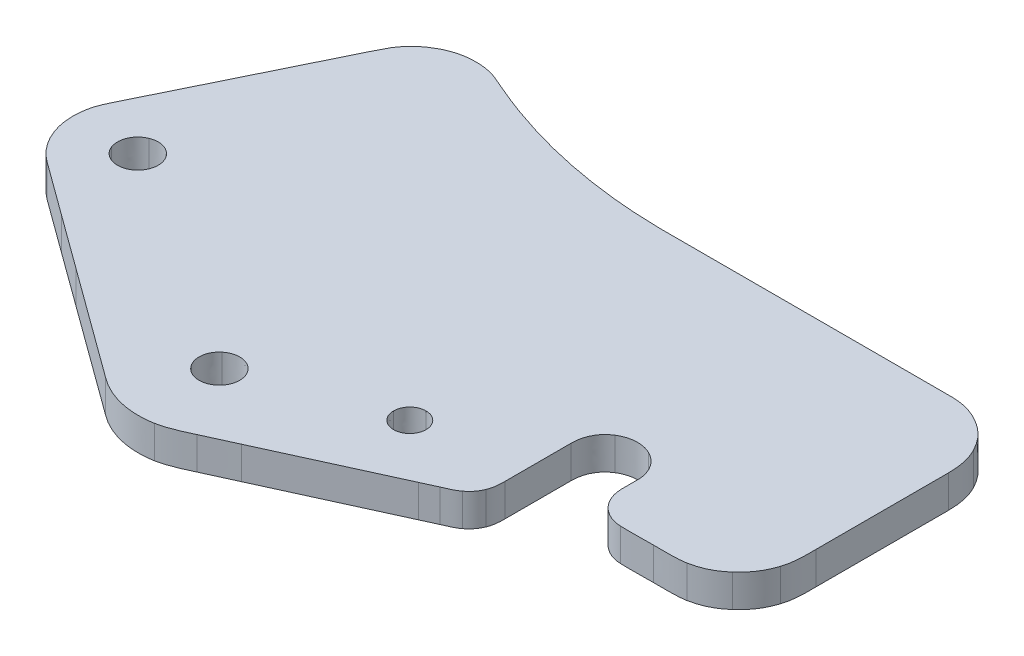
SolidWorks part; units mm, degrees
ref_plane "Front Plane" through (0, 0, 0) normal (0, 0, 1) x (1, 0, 0)
ref_plane "Top Plane" through (0, 0, 0) normal (0, 1, 0) x (1, 0, 0)
ref_plane "Right Plane" through (0, 0, 0) normal (1, 0, 0) x (0, 0, -1)
sketch "Imported Profile" plane through (0, 0, 0) normal (0, 1, 0) x (1, 0, 0)
  spline S0 degree 3 poles (47.6488, 3.4753) (40.593, 8.6202) (33.5375, 13.7602) (26.4819, 18.9072) knots 0 0 0 0 1 1 1 1
  spline S1 degree 3 poles (26.4819, 18.9072) (22.961, 21.4772) (19.4332, 24.0473) (15.9054, 26.6173) knots 0 0 0 0 1 1 1 1
  spline S2 degree 3 poles (15.9054, 26.6173) (12.3776, 29.1943) (8.8292, 31.7229) (5.329, 34.3343) knots 0 0 0 0 1 1 1 1
  spline S3 degree 3 poles (5.329, 34.3343) (1.7254, 37.0215) (-0.1832, 41.3968) (0.2923, 45.8616) knots 0 0 0 0 1 1 1 1
  spline S4 degree 3 poles (0.2923, 45.8616) (0.5679, 48.4454) (1.3534, 49.7752) (2.4489, 52.0214) knots 0 0 0 0 1 1 1 1
  spline S5 degree 3 poles (2.4489, 52.0214) (3.4066, 53.9851) (4.3713, 55.942) (5.329, 57.8988) knots 0 0 0 0 1 1 1 1
  spline S6 degree 3 poles (5.329, 57.8988) (9.1599, 65.7398) (12.9978, 73.5809) (16.8287, 81.4288) knots 0 0 0 0 1 1 1 1
  spline S7 degree 3 poles (16.8287, 81.4288) (17.2628, 82.3038) (19.1783, 86.3001) (19.7019, 87.1339) knots 0 0 0 0 1 1 1 1
  spline S8 degree 3 poles (19.7019, 87.1339) (20.9491, 89.1182) (22.4649, 90.5238) (24.532, 91.6194) knots 0 0 0 0 1 1 1 1
  spline S9 degree 3 poles (24.532, 91.6194) (26.6886, 92.7563) (28.7694, 93.2041) (31.2086, 93.0595) knots 0 0 0 0 1 1 1 1
  spline S10 degree 3 poles (31.2086, 93.0595) (33.8062, 92.9079) (34.9913, 92.2395) (37.2926, 91.2473) knots 0 0 0 0 1 1 1 1
  spline S11 degree 3 poles (37.2926, 91.2473) (45.3403, 87.754) (53.5052, 85.3975) (62.18, 84.0608) knots 0 0 0 0 1 1 1 1
  spline S12 degree 3 poles (62.18, 84.0608) (71.9503, 82.5519) (78.5373, 82.8688) (88.3283, 82.8688) knots 0 0 0 0 1 1 1 1
  spline S13 degree 3 poles (88.3283, 82.8688) (97.065, 82.8688) (105.8018, 82.8688) (114.5317, 82.8688) knots 0 0 0 0 1 1 1 1
  spline S14 degree 3 poles (114.5317, 82.8688) (118.8518, 82.8688) (123.1719, 82.8688) (127.499, 82.8688) knots 0 0 0 0 1 1 1 1
  spline S15 degree 3 poles (127.499, 82.8688) (129.6487, 82.8688) (131.7985, 82.9378) (133.9413, 82.8638) knots 0 0 0 0 1 1 1 1
  spline S16 degree 3 poles (133.9413, 82.8638) (136.2426, 82.7813) (138.1926, 82.1886) (140.1494, 80.9759) knots 0 0 0 0 1 1 1 1
  spline S17 degree 3 poles (140.1494, 80.9759) (142.244, 79.6874) (143.6978, 78.1096) (144.8071, 75.9116) knots 0 0 0 0 1 1 1 1
  spline S18 degree 3 poles (144.8071, 75.9116) (145.8338, 73.8928) (146.1783, 71.8946) (146.1783, 69.6692) knots 0 0 0 0 1 1 1 1
  spline S19 degree 3 poles (146.1783, 69.6692) (146.1783, 65.3489) (146.1783, 61.022) (146.1783, 56.7017) knots 0 0 0 0 1 1 1 1
  spline S20 degree 3 poles (146.1783, 56.7017) (146.1783, 52.3954) (146.1783, 48.089) (146.1783, 43.7827) knots 0 0 0 0 1 1 1 1
  spline S21 degree 3 poles (146.1783, 43.7827) (146.1783, 41.6536) (146.2543, 39.5865) (145.5788, 37.485) knots 0 0 0 0 1 1 1 1
  spline S22 degree 3 poles (145.5788, 37.485) (144.8416, 35.1768) (143.6909, 33.4061) (141.865, 31.8006) knots 0 0 0 0 1 1 1 1
  spline S23 degree 3 poles (141.865, 31.8006) (140.0805, 30.2296) (138.2063, 29.3133) (135.8637, 28.8654) knots 0 0 0 0 1 1 1 1
  spline S24 degree 3 poles (135.8637, 28.8654) (134.2514, 28.5624) (131.137, 28.6449) (129.5247, 28.6449) knots 0 0 0 0 1 1 1 1
  spline S25 degree 3 poles (129.5247, 28.6449) (127.3818, 28.6449) (125.2321, 28.5624) (123.0893, 28.6449) knots 0 0 0 0 1 1 1 1
  spline S26 degree 3 poles (123.0893, 28.6449) (120.7879, 28.7344) (118.714, 30.0574) (117.6736, 32.1107) knots 0 0 0 0 1 1 1 1
  spline S27 degree 3 poles (117.6736, 32.1107) (116.5849, 34.2328) (117.0741, 36.3137) (116.9708, 38.4427) knots 0 0 0 0 1 1 1 1
  spline S28 degree 3 poles (116.9708, 38.4427) (116.8538, 40.751) (115.5032, 42.8042) (113.4292, 43.824) knots 0 0 0 0 1 1 1 1
  spline S29 degree 3 poles (113.4292, 43.824) (111.4448, 44.8024) (109.1022, 44.6715) (107.2349, 43.4935) knots 0 0 0 0 1 1 1 1
  spline S30 degree 3 poles (107.2349, 43.4935) (105.1885, 42.1981) (104.279, 40.1655) (104.279, 37.8228) knots 0 0 0 0 1 1 1 1
  spline S31 degree 3 poles (104.279, 37.8228) (104.279, 33.5096) (104.279, 29.1963) (104.279, 24.8762) knots 0 0 0 0 1 1 1 1
  spline S32 degree 3 poles (104.279, 24.8762) (104.279, 23.7806) (104.224, 22.7471) (103.79, 21.6998) knots 0 0 0 0 1 1 1 1
  spline S33 degree 3 poles (103.79, 21.6998) (103.335, 20.618) (102.7014, 19.7981) (101.7643, 19.0884) knots 0 0 0 0 1 1 1 1
  spline S34 degree 3 poles (101.7643, 19.0884) (100.8824, 18.4201) (99.8833, 18.0618) (98.9049, 17.6208) knots 0 0 0 0 1 1 1 1
  spline S35 degree 3 poles (98.9049, 17.6208) (97.9265, 17.1728) (96.9481, 16.7251) (95.9628, 16.2772) knots 0 0 0 0 1 1 1 1
  spline S36 degree 3 poles (95.9628, 16.2772) (88.046, 12.6668) (80.1291, 9.0563) (72.2054, 5.4458) knots 0 0 0 0 1 1 1 1
  spline S37 degree 3 poles (72.2054, 5.4458) (70.2279, 4.5501) (68.2504, 3.6475) (66.2729, 2.7449) knots 0 0 0 0 1 1 1 1
  spline S38 degree 3 poles (66.2729, 2.7449) (64.2955, 1.8423) (62.3869, 0.8983) (60.2027, 0.4918) knots 0 0 0 0 1 1 1 1
  spline S39 degree 3 poles (60.2027, 0.4918) (55.7792, -0.335) (51.2248, 0.7468) (47.6488, 3.4753) knots 0 0 0 0 1 1 1 1
  spline S40 degree 3 poles (87.8115, 25.9559) (87.8115, 27.706) (86.3921, 29.1253) (84.6351, 29.1253) knots 0 0 0 0 1 1 1 1
  spline S41 degree 3 poles (84.6351, 29.1253) (82.8781, 29.1253) (81.4587, 27.706) (81.4587, 25.9559) knots 0 0 0 0 1 1 1 1
  spline S42 degree 3 poles (81.4587, 25.9559) (81.4587, 24.1988) (82.8781, 22.7795) (84.6351, 22.7795) knots 0 0 0 0 1 1 1 1
  spline S43 degree 3 poles (84.6351, 22.7795) (86.3921, 22.7795) (87.8115, 24.1988) (87.8115, 25.9559) knots 0 0 0 0 1 1 1 1
  spline S44 degree 3 poles (16.5876, 46.0339) (15.747, 48.0596) (13.425, 49.0242) (11.3993, 48.1836) knots 0 0 0 0 1 1 1 1
  spline S45 degree 3 poles (11.3993, 48.1836) (9.3735, 47.343) (8.4158, 45.021) (9.2495, 42.9953) knots 0 0 0 0 1 1 1 1
  spline S46 degree 3 poles (9.2495, 42.9953) (10.0901, 40.9696) (12.4121, 40.0118) (14.4378, 40.8455) knots 0 0 0 0 1 1 1 1
  spline S47 degree 3 poles (14.4378, 40.8455) (16.4635, 41.6862) (17.4213, 44.0081) (16.5876, 46.0339) knots 0 0 0 0 1 1 1 1
  spline S48 degree 3 poles (60.32, 18.6385) (58.914, 20.3197) (56.4129, 20.5402) (54.7317, 19.1275) knots 0 0 0 0 1 1 1 1
  spline S49 degree 3 poles (54.7317, 19.1275) (53.0505, 17.7219) (52.83, 15.2207) (54.2427, 13.5395) knots 0 0 0 0 1 1 1 1
  spline S50 degree 3 poles (54.2427, 13.5395) (55.6552, 11.8583) (58.1563, 11.6447) (59.8375, 13.0505) knots 0 0 0 0 1 1 1 1
  spline S51 degree 3 poles (59.8375, 13.0505) (61.5118, 14.4561) (61.7323, 16.9642) (60.32, 18.6385) knots 0 0 0 0 1 1 1 1
extrude "Boss-Extrude1" add sketch "Imported Profile" along normal blind 6.35
sketch "Sketch1" plane through (0, 6.35, 0) normal (0, 1, 0) x (1, 0, 0)
  circle A1 centre (77.6778, 184.4719) radius 101.6
  spline S2 degree 3 poles (88.3283, 82.8688) (78.5373, 82.8688) (71.9503, 82.5519) (62.18, 84.0608) knots 0 0 0 0 1 1 1 1 construction
  dimension "D1" = 203.2
sketch "Sketch2" plane through (0, 6.35, 0) normal (0, 1, 0) x (1, 0, 0)
  circle A1 centre (84.6351, 25.9559) radius 3.1764
  circle A2 centre (57.2811, 16.0861) radius 3.9686
  circle A3 centre (12.9185, 44.5146) radius 3.9712
  circle A4 centre (110.6276, 38.1193) radius 6.3555
